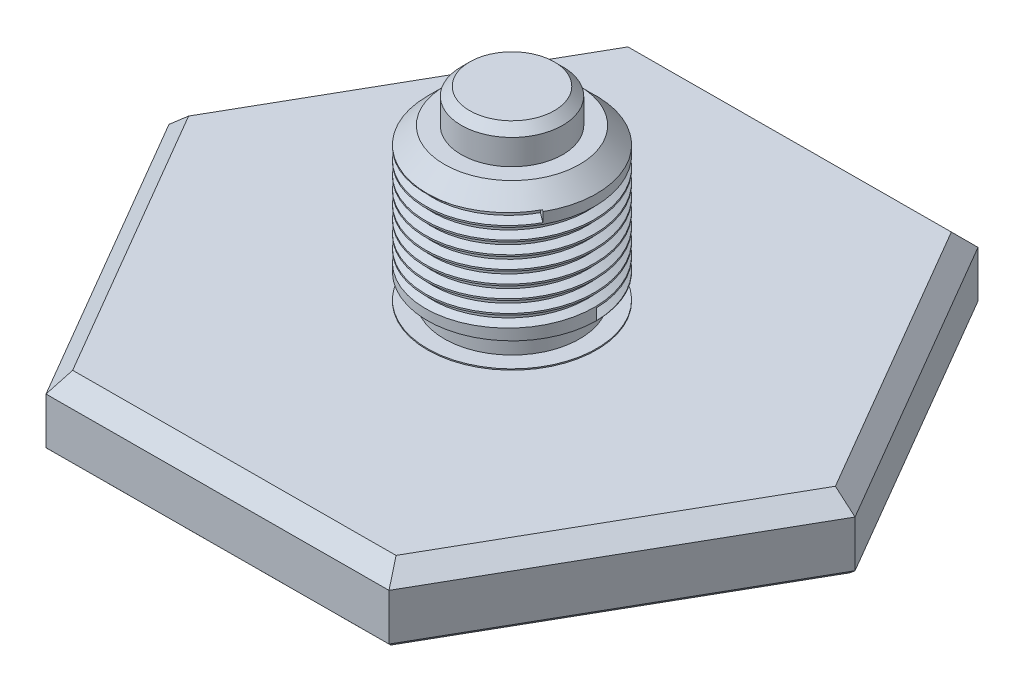
SolidWorks part; units mm, degrees
ref_plane "Front Plane" through (0, 0, 0) normal (0, 0, 1) x (1, 0, 0)
ref_plane "Top Plane" through (0, 0, 0) normal (0, 1, 0) x (1, 0, 0)
ref_plane "Right Plane" through (0, 0, 0) normal (1, 0, 0) x (0, 0, -1)
sketch "Sketch1" plane through (0, 0, 0) normal (0, 1, 0) x (1, 0, 0)
  line L1 (-20.3421, 34.8823) -> (-40.38, -0.1756)
  line L2 (-40.38, -0.1756) -> (-20.0379, -35.0579)
  line L3 (-20.0379, -35.0579) -> (20.3421, -34.8823)
  line L4 (20.3421, -34.8823) -> (40.38, 0.1756)
  line L5 (40.38, 0.1756) -> (20.0379, 35.0579)
  line L6 (20.0379, 35.0579) -> (-20.3421, 34.8823)
  circle A0 centre (0, 0) radius 34.9704 construction
  dimension "D1" = 40.38
  dimension "D2" = 69.9409
extrude "Boss-Extrude1" add sketch "Sketch1" along normal blind 8
chamfer "Chamfer1" distance 2 angle 45 6 edges at (0.1521, 8, 34.9701) (30.361, 8, 17.3534) (30.209, 8, -17.6167) (-0.1521, 8, -34.9701) (-30.361, 8, -17.3534) (-30.209, 8, 17.6167)
chamfer "Chamfer2" distance 0.5 angle 45 6 edges at (-30.361, 0, -17.3534) (-30.209, 0, 17.6167) (0.1521, 0, 34.9701) (30.361, 0, 17.3534) (30.209, 0, -17.6167) (-0.1521, 0, -34.9701)
sketch "Sketch42" plane through (0, 8, 0) normal (0, 1, 0) x (1, 0, 0)
  circle A0 centre (0, 0) radius 10
extrude "Boss-Extrude6" add sketch "Sketch42" along normal blind 18
chamfer "Chamfer3" distance 2 angle 45 1 edges at (0, 26, 10)
thread "Thread6" pitch 1.5 method cut profile "Thread Profile10" start angle 0, offset 3, length 0, pitch 1.5, diameter 20
ref_plane "Plane10" through (10, 11, 0) normal (0, 0, 1) x (1, 0, 0)
sketch "Thread Profile10" plane through (10, 11, 0) normal (0, 0, 1) x (1, 0, 0)
  line L0 (0, 0) -> (0, 1.5) construction
  line L11 (0, 0) -> (0, 1.3125)
  line L12 (0, 1.3125) -> (-0.8119, 0.8437)
  line L13 (-0.8119, 0.8437) -> (-0.8119, 0.4687)
  line L15 (-0.8119, 0.4687) -> (0, 0)
  line L17 (-0.8119, 0.6562) -> (0, 0.6562) construction
  point P2 (0, 0)
  dimension "Pitch" = 1.5
  dimension "Profile_Angle" = 60
  dimension "Profile_Land" = 0.375
  dimension "Profile_Height" = 0.8119
sketch3d "3DSketch5"
  line L1 (10, 11, 0) -> (10, 8.1353, 0)
  line L2 (10, 11, 0) -> (8.0043, 11, 0)
  line L3 (8.0043, 11, 0) -> (8.0043, 8.1353, 0)
  line L4 (10, 8.1353, 0) -> (8.0043, 8.1353, 0)
sketch "Sketch43" plane through (0, 8, 0) normal (0, 1, 0) x (1, 0, 0)
  line L0 (10, 0) -> (0, 0)
  circle A0 centre (0, 0) radius 10 construction
ref_plane "Plane12" through (0, 0, 0) normal (-0.0043, 0, -1) x (-1, 0, 0.0043)
sketch "Sketch44" plane through (0, 0, 0) normal (-0.0043, 0, -1) x (-1, 0, 0.0043)
  line L0 (0, 12.876) -> (0, 8)
  line L5 (-19.0355, 8) -> (19.0355, 8) construction
  spline S0 degree 2 poles (-9.9999, 11) (-10.0179, 11.0938) (-7.1017, 11.1875) (-4.1856, 11.2812) (-0.0435, 11.375) (4.0986, 11.4687) (7.0403, 11.5625) (9.9819, 11.6562) (9.9999, 11.75) (10.0179, 11.8437) (7.1017, 11.9375) (4.1856, 12.0312) (0.0435, 12.125) (-4.0986, 12.2187) (-7.0403, 12.3125) (-9.9819, 12.4063) (-9.9999, 12.5) (-10.0179, 12.5938) (-7.1017, 12.6875) (-4.1856, 12.7812) (-0.0435, 12.875) (4.0986, 12.9687) (7.0403, 13.0625) (9.9819, 13.1562) (9.9999, 13.25) (10.0179, 13.3437) (7.1017, 13.4375) (4.1856, 13.5312) (0.0435, 13.625) (-4.0986, 13.7187) (-7.0403, 13.8125) (-9.9819, 13.9063) (-9.9999, 14) (-10.0179, 14.0938) (-7.1017, 14.1875) (-4.1856, 14.2812) (-0.0435, 14.375) (4.0986, 14.4687) (7.0403, 14.5625) (9.9819, 14.6562) (9.9999, 14.75) (10.0179, 14.8437) (7.1017, 14.9375) (4.1856, 15.0312) (0.0435, 15.125) (-4.0986, 15.2187) (-7.0403, 15.3125) (-9.9819, 15.4063) (-9.9999, 15.5) (-10.0179, 15.5938) (-7.1017, 15.6875) (-4.1856, 15.7812) (-0.0435, 15.875) (4.0986, 15.9687) (7.0403, 16.0625) (9.9819, 16.1562) (9.9999, 16.25) (10.0179, 16.3437) (7.1017, 16.4375) (4.1856, 16.5312) (0.0435, 16.625) (-4.0986, 16.7187) (-7.0403, 16.8125) (-9.9819, 16.9063) (-9.9999, 17) (-10.0179, 17.0938) (-7.1017, 17.1875) (-4.1856, 17.2812) (-0.0435, 17.375) (4.0986, 17.4687) (7.0403, 17.5625) (9.9819, 17.6562) (9.9999, 17.75) (10.0179, 17.8437) (7.1017, 17.9375) (4.1856, 18.0312) (0.0435, 18.125) (-4.0986, 18.2187) (-7.0403, 18.3125) (-9.9819, 18.4063) (-9.9999, 18.5) (-10.0179, 18.5938) (-7.1017, 18.6875) (-4.1856, 18.7812) (-0.0435, 18.875) (4.0986, 18.9687) (7.0403, 19.0625) (9.9819, 19.1562) (9.9999, 19.25) (10.0179, 19.3437) (7.1017, 19.4375) (4.1856, 19.5312) (0.0435, 19.625) (-4.0986, 19.7187) (-7.0403, 19.8125) (-9.9819, 19.9063) (-9.9999, 20) (-10.0179, 20.0938) (-7.1017, 20.1875) (-4.1856, 20.2812) (-0.0435, 20.375) (4.0986, 20.4687) (7.0403, 20.5625) (9.9819, 20.6562) (9.9999, 20.75) (10.0179, 20.8437) (7.1017, 20.9375) (4.1856, 21.0312) (0.0435, 21.125) (-4.0986, 21.2187) (-7.0403, 21.3125) (-9.9819, 21.4063) (-9.9999, 21.5) (-10.0179, 21.5938) (-7.1017, 21.6875) (-4.1856, 21.7812) (-0.0435, 21.875) (4.0986, 21.9687) (7.0403, 22.0625) (9.9819, 22.1562) (9.9999, 22.25) (10.0179, 22.3437) (7.1017, 22.4375) (4.1856, 22.5312) (0.0435, 22.625) (-4.0986, 22.7187) (-7.0403, 22.8125) (-7.9752, 22.8423) (-8.6384, 22.8743) knots 0 0 0 0.015625 0.015625 0.03125 0.03125 0.046875 0.046875 0.0625 0.0625 0.078125 0.078125 0.09375 0.09375 0.109375 0.109375 0.125 0.125 0.140625 0.140625 0.15625 0.15625 0.171875 0.171875 0.1875 0.1875 0.203125 0.203125 0.21875 0.21875 0.234375 0.234375 0.25 0.25 0.265625 0.265625 0.28125 0.28125 0.296875 0.296875 0.3125 0.3125 0.328125 0.328125 0.34375 0.34375 0.359375 0.359375 0.375 0.375 0.390625 0.390625 0.40625 0.40625 0.421875 0.421875 0.4375 0.4375 0.453125 0.453125 0.46875 0.46875 0.484375 0.484375 0.5 0.5 0.515625 0.515625 0.53125 0.53125 0.546875 0.546875 0.5625 0.5625 0.578125 0.578125 0.59375 0.59375 0.609375 0.609375 0.625 0.625 0.640625 0.640625 0.65625 0.65625 0.671875 0.671875 0.6875 0.6875 0.703125 0.703125 0.71875 0.71875 0.734375 0.734375 0.75 0.75 0.765625 0.765625 0.78125 0.78125 0.796875 0.796875 0.8125 0.8125 0.828125 0.828125 0.84375 0.84375 0.859375 0.859375 0.875 0.875 0.890625 0.890625 0.90625 0.90625 0.921875 0.921875 0.9375 0.9375 0.953125 0.953125 0.96875 0.96875 0.984375 0.984375 0.989613 0.989613 0.989613 weights 1 0.92388 1 0.92388 1 0.92388 1 0.92388 1 0.92388 1 0.92388 1 0.92388 1 0.92388 1 0.92388 1 0.92388 1 0.92388 1 0.92388 1 0.92388 1 0.92388 1 0.92388 1 0.92388 1 0.92388 1 0.92388 1 0.92388 1 0.92388 1 0.92388 1 0.92388 1 0.92388 1 0.92388 1 0.92388 1 0.92388 1 0.92388 1 0.92388 1 0.92388 1 0.92388 1 0.92388 1 0.92388 1 0.92388 1 0.92388 1 0.92388 1 0.92388 1 0.92388 1 0.92388 1 0.92388 1 0.92388 1 0.92388 1 0.92388 1 0.92388 1 0.92388 1 0.92388 1 0.92388 1 0.92388 1 0.92388 1 0.92388 1 0.92388 1 0.92388 1 0.92388 1 0.92388 1 0.92388 1 0.92388 1 0.92388 1 0.92388 1 0.92388 1 0.92388 1 0.92388 1 0.92388 1 0.92388 1 0.92388 1 0.974481 0.966072 construction
revolve "Cut-Revolve1" cut sketch "3DSketch5" angle 360 mid plane about L0
ref_plane "Plane13" through (0, 26, 0) normal (0, 1, 0) x (1, 0, 0)
sketch "Sketch45" plane through (0, 26, 0) normal (0, 1, 0) x (1, 0, 0)
  circle A0 centre (0, 0) radius 6
extrude "Boss-Extrude7" add sketch "Sketch45" along normal blind 4
chamfer "Chamfer4" distance 1 angle 45 1 edges at (0, 30, 6)
sketch3d "3DSketch6"
  point P0 (0, 55, 0)
sketch3d "3DSketch7"
  point P0 (0, 15, 0)
